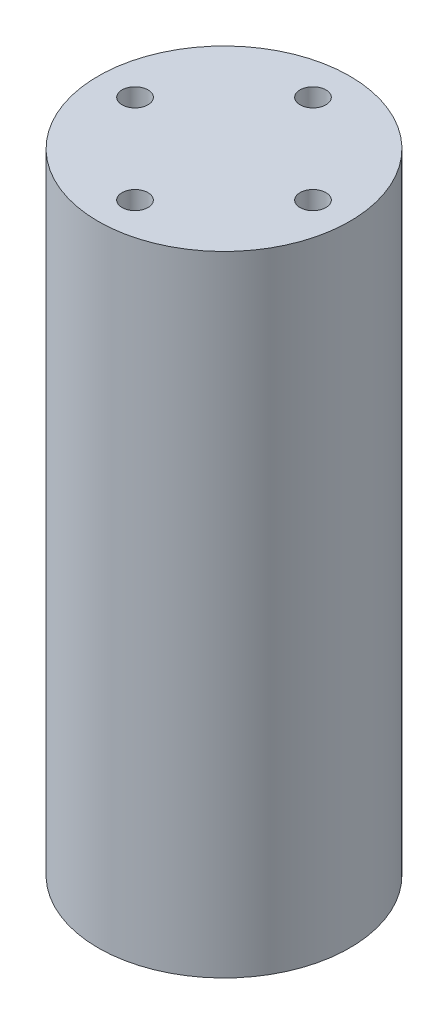
SolidWorks part; units mm, degrees
ref_plane "Front" through (0, 0, 0) normal (0, 0, 1) x (1, 0, 0)
ref_plane "Top" through (0, 0, 0) normal (0, 1, 0) x (1, 0, 0)
ref_plane "Right" through (0, 0, 0) normal (1, 0, 0) x (0, 0, -1)
sketch "Sketch1" plane through (0, 0, 0) normal (0, 1, 0) x (1, 0, 0)
  circle A0 centre (0, 0) radius 16
  circle A1 centre (0, 0) radius 11.3137
  circle A2 centre (0, -11.3137) radius 1.65
  circle A3 centre (11.3137, 0) radius 1.65
  circle A4 centre (0, 11.3137) radius 1.65
  circle A5 centre (-11.3137, 0) radius 1.65
extrude "Boss-Extrude1" add sketch "Sketch1" along normal blind 80 contours A5 A1 A2 A3 A4 | A0 A5 A1 A4 A3 A2 region at (-15.5475, 0, 0) region at (0, 0, 0)
